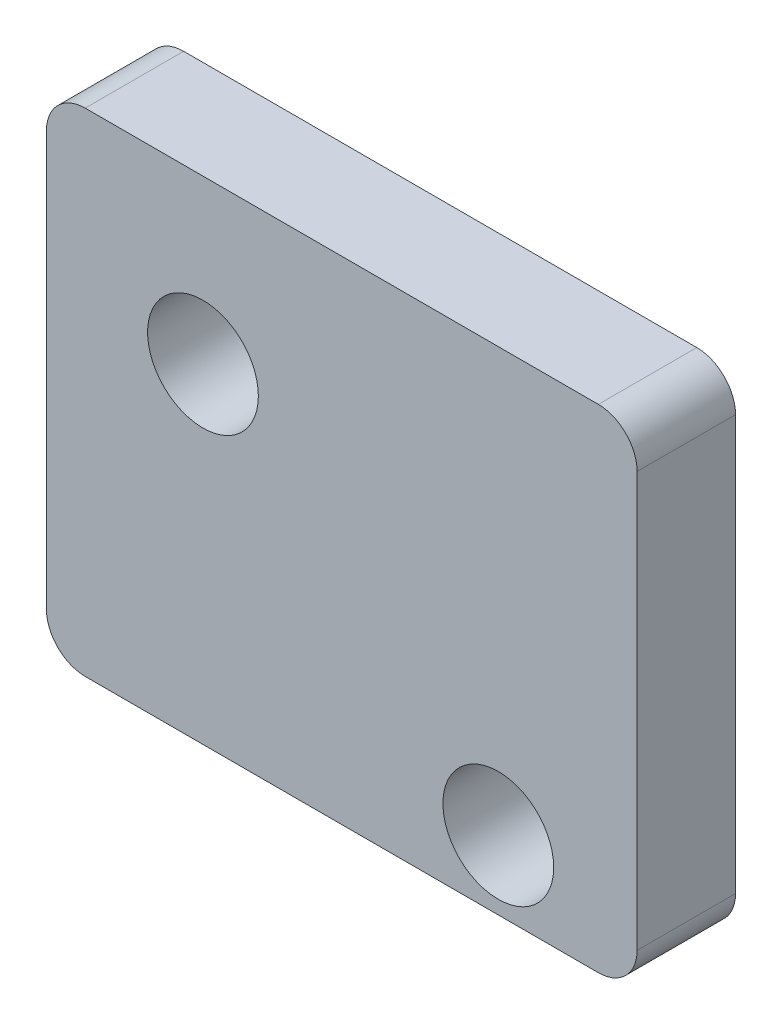
SolidWorks part; units mm, degrees
ref_plane "Front Plane" through (0, 0, 0) normal (0, 0, 1) x (1, 0, 0)
ref_plane "Top Plane" through (0, 0, 0) normal (0, 1, 0) x (1, 0, 0)
ref_plane "Right Plane" through (0, 0, 0) normal (1, 0, 0) x (0, 0, -1)
sketch "Sketch2" plane through (0, 0, 0) normal (0, 0, 1) x (1, 0, 0)
  line L0 (40.386, -42.0179) -> (116.586, -109.22) construction
  line L1 (0, 0) -> (152.4, 0)
  line L2 (0, 0) -> (0, -127)
  line L3 (0, -127) -> (152.4, -127)
  line L4 (152.4, 0) -> (152.4, -127)
  circle A4 centre (40.386, -42.0179) radius 14.2875
  circle A5 centre (116.586, -109.22) radius 14.2875
  circle A6 centre (40.386, -42.0179) radius 50.8 construction
  circle A7 centre (116.586, -109.22) radius 12.7 construction
  dimension "D3" = 28.575
  dimension "D4" = 28.575
  dimension "D1" = 101.6
  dimension "D2" = 17.78
  dimension "1" = 25.4
  dimension "D8" = 76.2
  dimension "D5" = 101.6
  dimension "D6" = 127
  dimension "D7" = 152.4
extrude "Boss-Extrude1" add sketch "Sketch2" along normal blind 25.4
fillet "Fillet2" radius 10 4 edges at (152.4, 0, 12.7) (152.4, -127, 12.7) (0, -127, 12.7) (0, 0, 12.7)
equation "\"length\"=3.09006"
